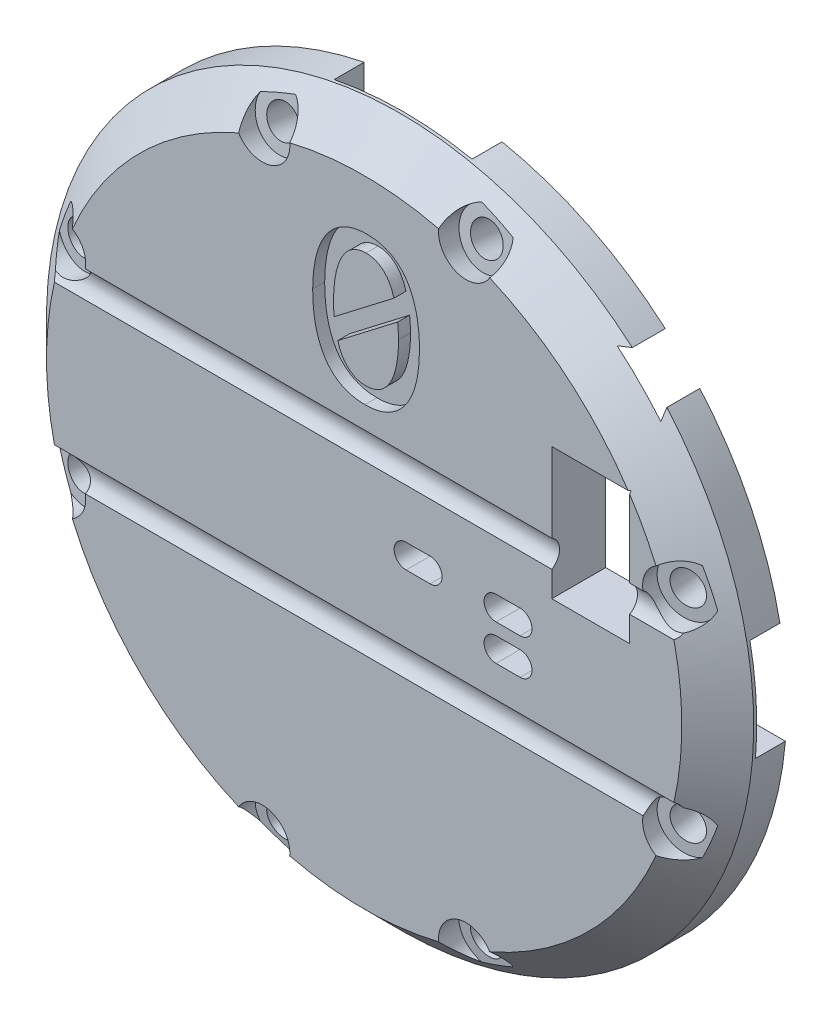
SolidWorks part; units mm, degrees
ref_plane "Front Plane" through (0, 0, 0) normal (0, 0, 1) x (1, 0, 0)
ref_plane "Top Plane" through (0, 0, 0) normal (0, 1, 0) x (1, 0, 0)
ref_plane "Right Plane" through (0, 0, 0) normal (1, 0, 0) x (0, 0, -1)
sketch "Sketch1" plane through (0, 0, 0) normal (0, 0, 1) x (1, 0, 0)
  circle A0 centre (0, 0) radius 29.5
  dimension "D1" = 59
extrude "Boss-Extrude1" add sketch "Sketch1" along normal blind 5.75
sketch "Sketch3" plane through (0, 0, 0) normal (0, 0, -1) x (-1, 0, 0)
  line L1 (-22.25, -22.25) -> (22.25, -22.25)
  line L2 (-22.25, -22.25) -> (-22.25, 22.25)
  line L3 (-22.25, 22.25) -> (22.25, 22.25)
  line L4 (22.25, -22.25) -> (22.25, 22.25)
  line L5 (-22.25, -22.25) -> (22.25, 22.25) construction
  line L6 (-22.25, 22.25) -> (22.25, -22.25) construction
  point P0 (0, 0)
  dimension "D1" = 44.5
extrude "Cut-Extrude1" cut sketch "Sketch3" against normal blind 3.25
sketch "Sketch26" plane through (0, 0, 0) normal (0, 0, -1) x (-1, 0, 0)
  line L1 (22.25, 19.3698) -> (22.25, 17.8098)
  line L2 (19.3698, -22.25) -> (17.8098, -22.25)
  line L3 (-22.25, -19.3698) -> (-22.25, -17.8098)
  line L4 (17.8098, 22.25) -> (19.3698, 22.25)
  line L6 (22.25, -17.8098) -> (22.25, -19.3698)
  line L7 (-17.8098, -22.25) -> (-19.3698, -22.25)
  arc A4 (-22.25, -19.3698) -> (-19.3698, -22.25) centre (0, 0) ccw
  arc A5 (-22.25, -17.8098) -> (-17.8098, -22.25) centre (0, 0) ccw
  arc A6 (22.25, 17.8098) -> (17.8098, 22.25) centre (0, 0) ccw
  arc A7 (22.25, 19.3698) -> (19.3698, 22.25) centre (0, 0) ccw
  arc A8 (17.8098, -22.25) -> (22.25, -17.8098) centre (0, 0) ccw
  arc A9 (19.3698, -22.25) -> (22.25, -19.3698) centre (0, 0) ccw
  dimension "D1" = 1
extrude "Boss-Extrude5" add sketch "Sketch26" against normal up to surface (3.25 mm away) up to face at (0, 0, 3.25)
chamfer "Chamfer2" distance 3 angle 45 1 edges at (29.5, 0, 5.75)
sketch "Sketch9" plane through (0, 0, 0) normal (1, 0, 0) x (0, 0, -1)
  line L0 (-26.5723, 0) -> (15.7273, 0) construction
  line L3 (-5.75, 26.5) -> (-5.75, -26.5) construction
  circle A0 centre (-6.4, 7) radius 1.3
  circle A1 centre (-6.4, -7) radius 1.3
  dimension "D1" = 2.6
  dimension "D2" = 14
  dimension "D3" = 0.65
extrude "Cut-Extrude5" cut sketch "Sketch9" against normal through all both and the other way through all
sketch "Sketch10" plane through (0, 0, 0) normal (0, 0, -1) x (-1, 0, 0)
  line L1 (22.0007, 5.75) -> (34.0342, 5.75)
  line L2 (22.0007, 5.75) -> (22.0007, -5.75)
  line L3 (22.0007, -5.75) -> (34.0342, -5.75)
  line L4 (34.0342, 5.75) -> (34.0342, -5.75)
  line L8 (-22.0007, -5.75) -> (-34.0342, -5.75)
  line L9 (-22.0007, -5.75) -> (-22.0007, 5.75)
  line L10 (-22.0007, 5.75) -> (-34.0342, 5.75)
  line L11 (-34.0342, -5.75) -> (-34.0342, 5.75)
  line L12 (-5.75, 22.0007) -> (-5.75, 34.0342)
  line L13 (-5.75, 22.0007) -> (5.75, 22.0007)
  line L14 (5.75, 22.0007) -> (5.75, 34.0342)
  line L15 (-5.75, 34.0342) -> (5.75, 34.0342)
  line L16 (5.75, -22.0007) -> (5.75, -34.0342) [skipped]
  line L17 (5.75, -22.0007) -> (-5.75, -22.0007) [skipped]
  line L18 (-5.75, -22.0007) -> (-5.75, -34.0342) [skipped]
  line L19 (5.75, -34.0342) -> (-5.75, -34.0342) [skipped]
  point P4 (22.0007, 0)
  point P21 (0, 0)
  dimension "D1" = 11.5
  dimension "D2" = 4
extrude "Cut-Extrude6" cut sketch "Sketch10" against normal blind 2.5
sketch "Sketch13" plane through (0, 0, 3.25) normal (0, 0, -1) x (-1, 0, 0)
  line L0 (-22.25, 18.5994) -> (-22.25, -17.8098) construction
  line L1 (-22.15, 14.75) -> (-15.65, 14.75)
  line L2 (-22.15, 14.75) -> (-22.15, 3.75)
  line L3 (-22.15, 3.75) -> (-15.65, 3.75)
  line L4 (-15.65, 14.75) -> (-15.65, 3.75)
  line L5 (17.8098, 22.25) -> (-18.5994, 22.25) construction
  point P23 (0, 0)
  dimension "D1" = 0.1
  dimension "D2" = 7.5
  dimension "D4" = 11
  dimension "D3" = 6.5
extrude "Cut-Extrude9" cut sketch "Sketch13" against normal through all
sketch "Sketch14" plane through (0, 0, 0) normal (0, 0, -1) x (-1, 0, 0)
  line L1 (-35.1198, 0) -> (-19.2322, 0)
  line L2 (-35.1198, 0) -> (-35.1198, -11.6)
  line L3 (-35.1198, -11.6) -> (-19.2322, -11.6)
  line L4 (-19.2322, 0) -> (-19.2322, -11.6)
  dimension "D1" = 11.6
extrude "Cut-Extrude10" cut sketch "Sketch14" against normal up to surface (2.5 mm away) up to face at (25.7335, 0, 2.5)
sketch "Sketch15" plane through (0, 0, 5.75) normal (0, 0, 1) x (1, 0, 0)
  line L0 (0, 0) -> (12.0208, 12.0208) construction
  line L1 (0, 0) -> (36.7921, 0) construction
  circle A0 centre (12.0208, 12.0208) radius 12.5
  circle A1 centre (0, 0) radius 29.5 construction
  dimension "D2" = 25
  dimension "D1" = 45
ref_axis "Axis1" through (0, 0, -0.2945) along (0, 0, 1)
ref_axis "Axis2" through (0, 31.9, 0) along (0, -1, 0)
ref_plane "Plane1" through (0, 0, 0) normal (0.1392, 0, 0.9903) x (0, -1, 0)
sketch "Sketch23" plane through (0, 0, 2.5) normal (0, 0, -1) x (-1, 0, 0)
  line L0 (-22.25, -2.55) -> (-29.3896, -2.55)
  line L1 (-22.25, -2.55) -> (-22.25, -11.6)
  line L2 (-22.25, -11.6) -> (-27.1236, -11.6)
  line L3 (-22.25, 5.75) -> (-28.9342, 5.75) construction
  arc A0 (-29.3896, -2.55) -> (-27.1236, -11.6) centre (0, 0) ccw
  arc A1 (-28.9342, 5.75) -> (-27.1236, -11.6) centre (0, 0) ccw construction
  dimension "D1" = 8.3
extrude "Boss-Extrude3" add sketch "Sketch23" along normal up to surface (2.5 mm away) up to face at (10.4356, 24.7749, 0)
sketch "Sketch17" plane through (0, 0, 0) normal (0.1392, 0, 0.9903) x (0, -1, 0)
  line L0 (0, 0) -> (0, 33.2124) construction
  line L1 (0, 0.041) -> (0, -0.8607) construction
  circle A0 centre (-8.5, 24.5) radius 1.35
  circle A1 centre (8.5, 24.5) radius 1.35
  dimension "D1" = 2.7
  dimension "D2" = 17
  dimension "D3" = 24.5
extrude "Cut-Extrude12" cut sketch "Sketch17" along normal through all
sketch "Sketch18" plane through (0, 0, 0) normal (0.1392, 0, 0.9903) x (0, -1, 0)
  circle A0 centre (-8.5, 24.5) radius 2.3
  circle A1 centre (8.5, 24.5) radius 2.3
  dimension "D1" = 4.6
extrude "Cut-Extrude13" cut sketch "Sketch18" against normal blind 12.5 from offset 20
pattern_circular "CirPattern1" count 4 over 360 about axis through (0, 0, -0.2945) along (0, 0, 1) of "Cut-Extrude12", "Cut-Extrude13"
sketch "Sketch19" plane through (0, 0, 5.75) normal (0, 0, 1) x (1, 0, 0)
  line L0 (3.5, 0.75) -> (5.5, 0.75) construction
  line L1 (3.5, 1.75) -> (5.5, 1.75)
  line L2 (3.5, -0.25) -> (5.5, -0.25)
  line L3 (11, 0.75) -> (13, 0.75) construction
  line L4 (11, 1.75) -> (13, 1.75)
  line L5 (11, -0.25) -> (13, -0.25)
  line L6 (11, -2.25) -> (13, -2.25) construction
  line L7 (11, -1.25) -> (13, -1.25)
  line L8 (11, -3.25) -> (13, -3.25)
  arc A0 (3.5, 1.75) -> (3.5, -0.25) centre (3.5, 0.75) ccw
  arc A1 (5.5, -0.25) -> (5.5, 1.75) centre (5.5, 0.75) ccw
  arc A2 (11, 1.75) -> (11, -0.25) centre (11, 0.75) ccw
  arc A3 (13, -0.25) -> (13, 1.75) centre (13, 0.75) ccw
  arc A4 (11, -1.25) -> (11, -3.25) centre (11, -2.25) ccw
  arc A5 (13, -3.25) -> (13, -1.25) centre (13, -2.25) ccw
  point P2 (4.5, 0.75)
  point P8 (12, 0.75)
  point P16 (12, -2.25)
  dimension "D1" = 1
  dimension "D2" = 3
  dimension "D3" = 7.5
  dimension "D4" = 4.5
  dimension "D5" = 2
  dimension "D6" = 0.75
extrude "Cut-Extrude14" cut sketch "Sketch19" against normal through all
sketch "Sketch21" plane through (0, 0, 3.25) normal (0, 0, -1) x (-1, 0, 0)
  line L61 (-5.5, -0.35) -> (-3.5, -0.35)
  line L62 (-3.5, 1.85) -> (-5.5, 1.85)
  line L63 (-5.5, -0.35) -> (-3.5, -0.35)
  line L64 (-3.5, 1.85) -> (-5.5, 1.85)
  line L69 (-11, 1.85) -> (-13, 1.85)
  line L70 (-13, -0.35) -> (-11, -0.35)
  line L71 (-11, 1.85) -> (-13, 1.85)
  line L72 (-13, -0.35) -> (-11, -0.35)
  line L75 (-5.5, -1.35) -> (-3.5, -1.35)
  line L76 (-3.5, 2.85) -> (-5.5, 2.85)
  line L77 (-11, -1.15) -> (-13, -1.15)
  line L78 (-13, -3.35) -> (-11, -3.35)
  line L79 (-11, -1.15) -> (-13, -1.15)
  line L80 (-13, -3.35) -> (-11, -3.35)
  line L81 (-11, 2.85) -> (-13, 2.85)
  line L84 (-13, -4.35) -> (-11, -4.35)
  line L85 (-13, -1.35) -> (-11, -1.35) construction
  line L86 (-11, -0.15) -> (-13, -0.15) construction
  arc A55 (-5.5, 1.85) -> (-5.5, -0.35) centre (-5.5, 0.75) ccw
  arc A56 (-3.5, -0.35) -> (-3.5, 1.85) centre (-3.5, 0.75) ccw
  arc A57 (-5.5, 1.85) -> (-5.5, -0.35) centre (-5.5, 0.75) ccw
  arc A58 (-3.5, -0.35) -> (-3.5, 1.85) centre (-3.5, 0.75) ccw
  arc A65 (-13, 1.85) -> (-13, -0.35) centre (-13, 0.75) ccw
  arc A66 (-11, -0.35) -> (-11, 1.85) centre (-11, 0.75) ccw
  arc A67 (-13, 1.85) -> (-13, -0.35) centre (-13, 0.75) ccw
  arc A68 (-11, -0.35) -> (-11, 1.85) centre (-11, 0.75) ccw
  arc A73 (-5.5, 2.85) -> (-5.5, -1.35) centre (-5.5, 0.75) ccw
  arc A74 (-3.5, -1.35) -> (-3.5, 2.85) centre (-3.5, 0.75) ccw
  arc A75 (-13, -1.15) -> (-13, -3.35) centre (-13, -2.25) ccw
  arc A76 (-11, -3.35) -> (-11, -1.15) centre (-11, -2.25) ccw
  arc A77 (-13, -1.15) -> (-13, -3.35) centre (-13, -2.25) ccw
  arc A78 (-11, -3.35) -> (-11, -1.15) centre (-11, -2.25) ccw
  arc A80 (-13, 2.85) -> (-14.4697, -0.75) centre (-13, 0.75) ccw
  arc A81 (-11, -4.35) -> (-9.5303, -0.75) centre (-11, -2.25) ccw
  arc A84 (-9.5303, -0.75) -> (-11, 2.85) centre (-11, 0.75) ccw
  arc A85 (-11, -4.35) -> (-11, -0.15) centre (-11, -2.25) ccw construction
  arc A86 (-14.4697, -0.75) -> (-13, -4.35) centre (-13, -2.25) ccw
  arc A87 (-11, -1.35) -> (-11, 2.85) centre (-11, 0.75) ccw construction
  arc A88 (-13, 2.85) -> (-13, -1.35) centre (-13, 0.75) ccw construction
  arc A90 (-13, -0.15) -> (-13, -4.35) centre (-13, -2.25) ccw construction
  dimension "D1" = 0.1
  dimension "D2" = 0.1
  dimension "D3" = 0.1
  dimension "D4" = 1
  dimension "D5" = 1
extrude "Boss-Extrude2" add sketch "Sketch21" along normal blind 2
fillet "Fillet1" radius 1 7 edges at (7.6, 0.75, 3.25) (4.5, 2.85, 3.25) (1.4, 0.75, 3.25) (14.9442, -3.0437, 3.25) (9.0558, -3.0437, 3.25) (4.5, -1.35, 3.25) (12, -4.35, 3.25)
sketch "Sketch24" plane through (0, 0, 5.75) normal (0, 0, 1) x (1, 0, 0)
  line L0 (-5.1692, 10.1499) -> (12.5197, 10.1499) construction
  line L1 (0, 0) -> (0, 40.6298) construction
  text T0 "0" font "Consolas" height in points 46
extrude "Cut-Extrude16" cut sketch "Sketch24" against normal blind 1
sketch "Sketch25" plane through (0, 0, 3.25) normal (0, 0, -1) x (-1, 0, 0)
  line L0 (-22.25, 15.75) -> (-22.25, 14.75)
  line L1 (-22.25, 5.75) -> (-22.25, 19.3698) construction
  line L2 (-22.25, 14.75) -> (-15.65, 14.75)
  line L3 (-15.65, 14.75) -> (-15.65, 3.75)
  line L4 (-15.65, 3.75) -> (-22.25, 3.75)
  line L5 (-22.25, -2.55) -> (-22.25, 5.75) construction
  line L6 (-22.25, 3.75) -> (-22.25, 2.75)
  line L7 (-22.25, 2.75) -> (-14.65, 2.75)
  line L8 (-14.65, 2.75) -> (-14.65, 15.75)
  line L9 (-14.65, 15.75) -> (-22.25, 15.75)
  dimension "D1" = 1
  dimension "D2" = 1
  dimension "D3" = 1
extrude "Boss-Extrude4" add sketch "Sketch25" along normal blind 2
chamfer "Chamfer3" distance 0.5 angle 45 3 edges at (18.45, 15.75, 1.25) (18.45, 2.75, 1.25) (14.65, 9.25, 1.25)
